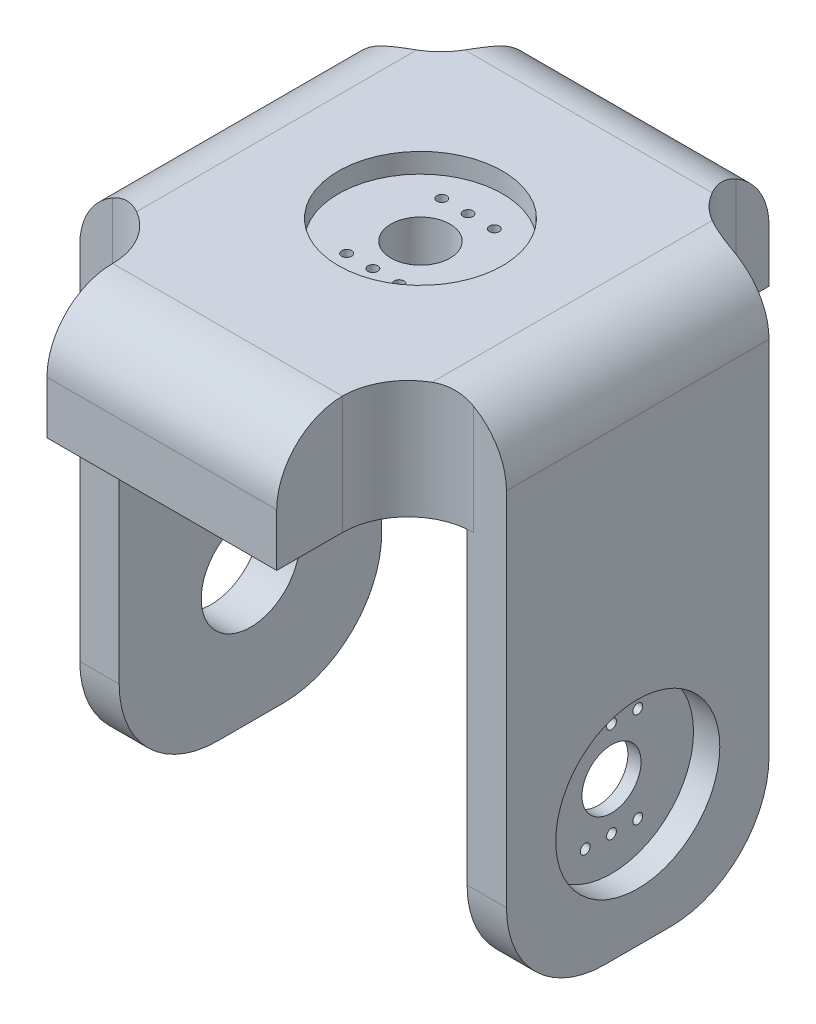
SolidWorks part; units mm, degrees
ref_plane "Front Plane" through (0, 0, 0) normal (0, 0, 1) x (1, 0, 0)
ref_plane "Top Plane" through (0, 0, 0) normal (0, 1, 0) x (1, 0, 0)
ref_plane "Right Plane" through (0, 0, 0) normal (1, 0, 0) x (0, 0, -1)
sketch "Sketch1" plane through (0, 0, 0) normal (0, 0, 1) x (1, 0, 0)
  line L0 (-26.5, -40) -> (-26.5, 22)
  line L1 (-32.5, -40) -> (-26.5, -40)
  line L2 (-32.5, -40) -> (-32.5, 40)
  line L3 (-32.5, 40) -> (32.5, 40)
  line L4 (32.5, -40) -> (32.5, 40)
  line L5 (-32.5, -40) -> (32.5, 40) construction
  line L6 (-32.5, 40) -> (32.5, -40) construction
  line L7 (-26.5, 22) -> (26.5, 22)
  line L8 (26.5, 22) -> (26.5, -40)
  line L9 (26.5, -40) -> (32.5, -40)
  point P0 (0, 0)
  dimension "D1" = 80
  dimension "D2" = 6
  dimension "D3" = 6
  dimension "D4" = 65
  dimension "D5" = 18
extrude "Boss-Extrude1" add sketch "Sketch1" along normal blind 40
sketch "Sketch2" plane through (32.5, 0, 0) normal (1, 0, 0) x (0, 0, -1)
  line L1 (-40, -40) -> (0, -40) construction
  circle A0 centre (-20, -20) radius 12.5
  dimension "D1" = 25
  dimension "D2" = 20
  dimension "D3" = 20
extrude "Cut-Extrude1" cut sketch "Sketch2" against normal blind 4
sketch "Sketch3" plane through (28.5, 0, 0) normal (1, 0, 0) x (0, 0, -1)
  line L0 (-29.7163, -20) -> (11.7737, -20) construction
  circle A1 centre (-20, -12.75) radius 0.75
  circle A2 centre (-16, -12.75) radius 0.75
  circle A3 centre (-24, -12.75) radius 0.75
  circle A7 centre (-20, -20) radius 4.5
  circle A8 centre (-16, -27.25) radius 0.75
  circle A9 centre (-20, -27.25) radius 0.75
  circle A10 centre (-24, -27.25) radius 0.75
  dimension "D2" = 1.5
  dimension "D6" = 9
  dimension "D3" = 7.25
  dimension "D4" = 4
  dimension "D5" = 4
extrude "Cut-Extrude2" cut sketch "Sketch3" against normal blind 4
sketch "Sketch4" plane through (-26.5, 0, 0) normal (1, 0, 0) x (0, 0, -1)
  circle A0 centre (-20, -20) radius 7.5
  circle A1 centre (-20, -20) radius 12.5 construction
  dimension "D1" = 15
extrude "Cut-Extrude3" cut sketch "Sketch4" against normal blind 14
sketch "Sketch7" plane through (0, 40, 0) normal (0, 1, 0) x (1, 0, 0)
  line L0 (32.5, 0) -> (-32.5, 0) construction
  line L1 (-17.5, 0) -> (17.5, 0)
  line L2 (-17.5, 0) -> (-17.5, 15)
  line L3 (-17.5, 15) -> (17.5, 15)
  line L4 (17.5, 0) -> (17.5, 15)
  line L5 (32.5, -40) -> (-32.5, -40) construction
  line L6 (-17.5, -40) -> (17.5, -40)
  line L7 (-17.5, -40) -> (-17.5, -60)
  line L8 (-17.5, -60) -> (17.5, -60)
  line L9 (17.5, -40) -> (17.5, -60)
  dimension "D1" = 15
  dimension "D2" = 20
  dimension "D3" = 35
extrude "Boss-Extrude2" add sketch "Sketch7" against normal up to surface (18 mm away) up to face at (0, 22, 20)
sketch "Sketch8" plane through (0, 22, 0) normal (0, -1, 0) x (1, 0, 0)
  line L1 (-12.5, 57) -> (12.5, 57)
  line L2 (-12.5, 57) -> (-12.5, 2)
  line L3 (-12.5, 2) -> (12.5, 2)
  line L4 (12.5, 57) -> (12.5, 2)
  line L5 (-12.5, 57) -> (12.5, 2) construction
  line L6 (-12.5, 2) -> (12.5, 57) construction
  line L7 (-17.5, -15) -> (17.5, -15) construction
  point P0 (0, 29.5)
  dimension "D1" = 17
  dimension "D2" = 55
  dimension "D3" = 25
extrude "Cut-Extrude7" cut sketch "Sketch8" against normal blind 4 contours L3 L4 L1 L2
sketch "Sketch9" plane through (0, 26, 0) normal (0, -1, 0) x (1, 0, 0)
  line L1 (-10, 49.5) -> (10, 49.5)
  line L2 (-10, 49.5) -> (-10, 9.5)
  line L3 (-10, 9.5) -> (10, 9.5)
  line L4 (10, 49.5) -> (10, 9.5)
  line L5 (-10, 49.5) -> (10, 9.5) construction
  line L6 (-10, 9.5) -> (10, 49.5) construction
  line L7 (-12.5, 57) -> (12.5, 57) construction
  point P0 (0, 29.5)
  dimension "D1" = 20
  dimension "D2" = 40
  dimension "D3" = 7.5
extrude "Cut-Extrude8" cut sketch "Sketch9" against normal blind 3
sketch "Sketch10" plane through (0, 40, 0) normal (0, 1, 0) x (1, 0, 0)
  line L0 (17.5, 15) -> (-17.5, 15) construction
  circle A0 centre (0, -20.6) radius 12.5
  dimension "D1" = 35.6
  dimension "D2" = 25
extrude "Cut-Extrude9" cut sketch "Sketch10" against normal blind 3
sketch "Sketch11" plane through (0, 37, 0) normal (0, 1, 0) x (1, 0, 0)
  line L0 (-8.1646, -20.6) -> (18.293, -20.6) construction
  circle A0 centre (0, -20.6) radius 4.5
  circle A1 centre (0, -13.35) radius 0.75
  circle A2 centre (4, -13.35) radius 0.75
  circle A3 centre (-4, -13.35) radius 0.75
  circle A4 centre (4, -27.85) radius 0.75
  circle A5 centre (0, -27.85) radius 0.75
  circle A6 centre (-4, -27.85) radius 0.75
  dimension "D1" = 9
  dimension "D2" = 1.5
  dimension "D3" = 7.25
  dimension "D4" = 8
  dimension "D5" = 4
extrude "Cut-Extrude10" cut sketch "Sketch11" against normal blind 13
fillet "Fillet1" radius 15 4 edges at (-29.5, -40, 0) (-29.5, -40, 40) (29.5, -40, 0) (29.5, -40, 40)
fillet "Fillet2" radius 10 4 edges at (-17.5, 31, 0) (17.5, 31, 0) (17.5, 31, 40) (-17.5, 31, 40)
fillet "Fillet3" radius 10 4 edges at (0, 40, -15) (0, 40, 60) (32.5, 40, 20) (-32.5, 40, 20)
